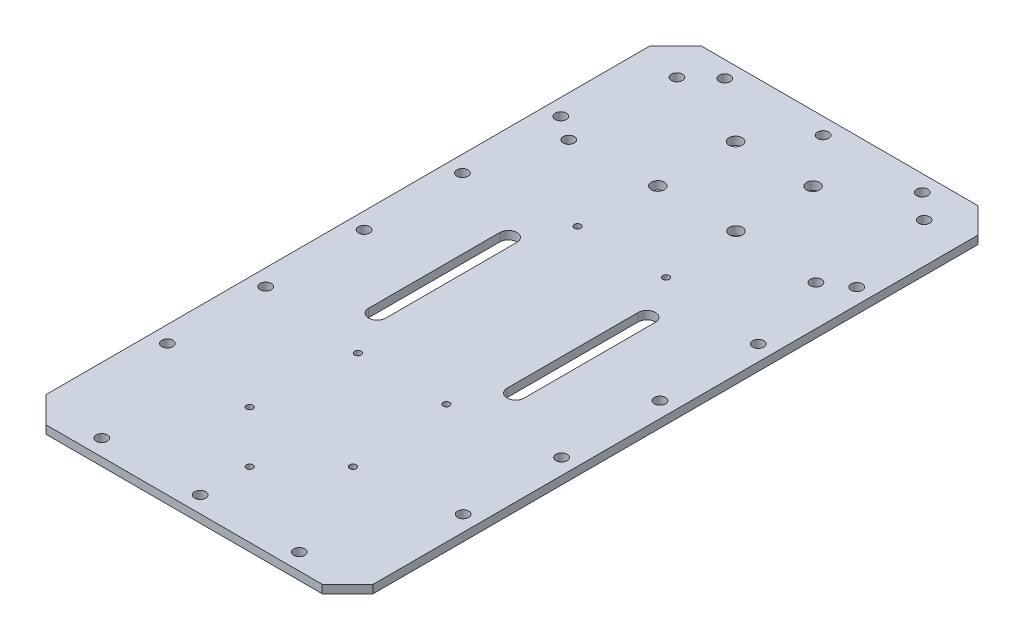
SolidWorks part; units mm, degrees
ref_plane "Front Plane" through (0, 0, 0) normal (0, 0, 1) x (1, 0, 0)
ref_plane "Top Plane" through (0, 0, 0) normal (0, 1, 0) x (1, 0, 0)
ref_plane "Right Plane" through (0, 0, 0) normal (1, 0, 0) x (0, 0, -1)
sketch "Sketch2" plane through (0, 0, 0) normal (0, 1, 0) x (1, 0, 0)
  line L0 (0, 10.1429) -> (0, 243.8571)
  line L1 (10.1429, 254) -> (117.1429, 254)
  line L2 (127, 244.1429) -> (127, 9.8571)
  line L3 (117.1429, 0) -> (10.1429, 0)
  line L4 (0, 243.8571) -> (10.1429, 254)
  line L5 (117.1429, 254) -> (127, 244.1429)
  line L6 (127, 9.8571) -> (117.1429, 0)
  line L7 (10.1429, 0) -> (0, 10.1429)
  line L8 (63.6429, 254) -> (63.6429, -22.4759) construction
  line L10 (0, 127) -> (136.1553, 127) construction
  line L11 (36.8271, 152.4) -> (36.8271, 101.6) construction
  line L15 (33.5113, 152.4) -> (33.5113, 101.6)
  line L16 (40.1429, 152.4) -> (40.1429, 101.6)
  line L32 (90.4588, 152.4) -> (90.4588, 101.6) construction
  line L42 (93.7746, 152.4) -> (93.7746, 101.6)
  line L43 (87.1429, 152.4) -> (87.1429, 101.6)
  circle A1 centre (6.35, 165.1) radius 2.159
  circle A13 centre (25.4, 247.65) radius 2.159
  circle A17 centre (15.7639, 238.76) radius 2.159
  circle A18 centre (15.7639, 196.85) radius 2.159
  circle A22 centre (46.4979, 169.545) radius 1.27
  circle A27 centre (48.643, 228.5997) radius 2.54
  circle A34 centre (48.5, 198.6001) radius 2.54
  circle A42 centre (6.35, 203.2) radius 2.159
  circle A43 centre (63.5, 247.65) radius 2.159
  circle A46 centre (6.35, 127) radius 2.159
  arc A52 (93.7746, 152.4) -> (87.1429, 152.4) centre (90.4588, 152.4) ccw
  arc A53 (87.1429, 101.6) -> (93.7746, 101.6) centre (90.4588, 101.6) ccw
  arc A54 (33.5113, 152.4) -> (40.1429, 152.4) centre (36.8271, 152.4) cw
  arc A55 (40.1429, 101.6) -> (33.5113, 101.6) centre (36.8271, 101.6) cw
  circle A56 centre (120.9359, 127) radius 2.159
  circle A57 centre (120.9359, 165.1) radius 2.159
  circle A58 centre (120.9359, 203.2) radius 2.159
  circle A59 centre (101.8859, 247.65) radius 2.159
  circle A60 centre (101.8859, 6.35) radius 2.159
  circle A61 centre (63.5, 6.35) radius 2.159
  circle A62 centre (25.4, 6.35) radius 2.159
  circle A63 centre (120.9359, 50.8) radius 2.159
  circle A64 centre (6.35, 50.8) radius 2.159
  circle A65 centre (120.9359, 88.9) radius 2.159
  circle A66 centre (6.35, 88.9) radius 2.159
  circle A67 centre (78.7858, 198.6001) radius 2.54
  circle A68 centre (78.6429, 228.5997) radius 2.54
  circle A69 centre (80.7879, 169.545) radius 1.27
  circle A70 centre (80.7879, 84.455) radius 1.27
  circle A71 centre (46.4979, 84.455) radius 1.27
  circle A72 centre (111.5219, 196.85) radius 2.159
  circle A73 centre (111.5219, 238.76) radius 2.159
  circle A74 centre (43.6429, 45.4) radius 1.27
  circle A75 centre (83.6429, 45.4) radius 1.27
  circle A76 centre (63.6429, 25.4) radius 1.27
  point P0 (0, 0)
  point P1 (0, 254)
  point P3 (127, 254)
  point P4 (127, 0)
  point P23 (90.4588, 127)
  point P36 (0, 0)
  point P71 (36.8271, 127)
  point P97 (0, 0)
  dimension "D2" = 254
  dimension "D8" = 95.758
  dimension "D9" = 29.9999
  dimension "D10" = 50.8
  dimension "D11" = 23.5
  dimension "D13" = 85.09
  dimension "D14" = 45
  dimension "D16" = 45
  dimension "D17" = 45
  dimension "D18" = 41.91
  dimension "D20" = 25.4
  dimension "D23" = 2.54
  dimension "D24" = 38.1
  dimension "D25" = 2.54
  dimension "D26" = 29.9999
  dimension "D27" = 5.08
  dimension "D28" = 5.08
  dimension "D29" = 2.54
  dimension "D30" = 38.1
  dimension "D31" = 40
  dimension "D32" = 4.318
  dimension "D33" = 4.318
  dimension "D34" = 20
  dimension "D35" = 20
  dimension "D44" = 4.318
  dimension "D45" = 6.35
  dimension "D50" = 4.318
  dimension "D51" = 6.35
  dimension "D55" = 2.54
  dimension "D12" = 34.29
  dimension "D7" = 127
  dimension "D15" = 45
  dimension "D19" = 15.24
  dimension "D67" = 38.1
extrude "Boss-Extrude1" add sketch "Sketch2" along normal blind 3.175 contours L7 L3 L6 L2 L5 L1 L4 L0 A46 A76 A66 A43 A42 A53 A34 A68 A64 A70 A22 A72 A18 A17 A13 A59 A56 region at (63.5056, 0, -126.6441)
